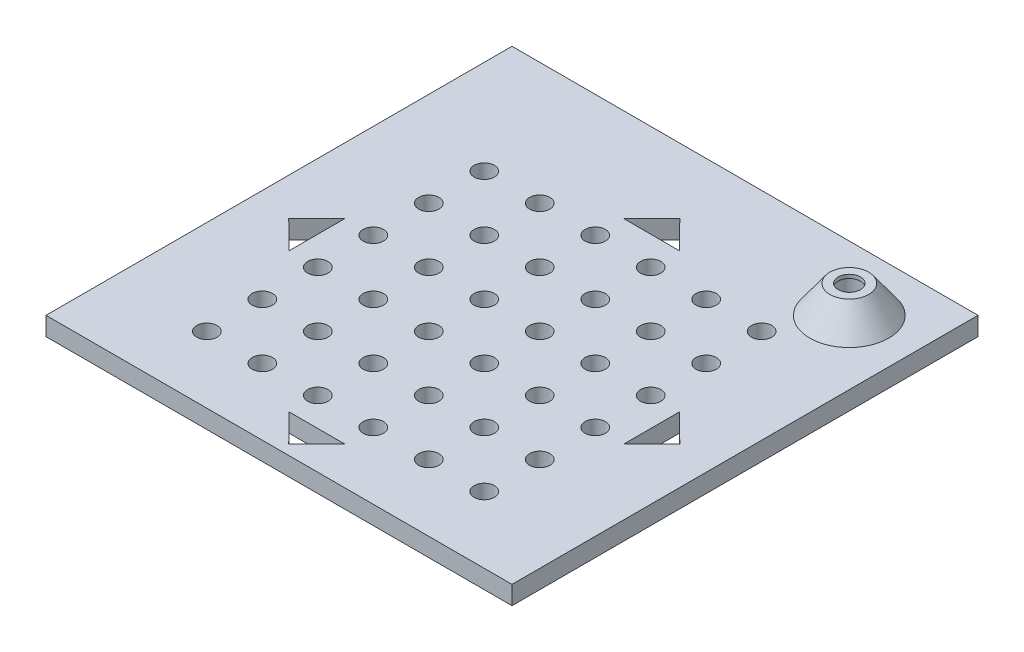
SolidWorks part; units mm, degrees
ref_plane "Front Plane" through (0, 0, 0) normal (0, 0, 1) x (1, 0, 0)
ref_plane "Top Plane" through (0, 0, 0) normal (0, 1, 0) x (1, 0, 0)
ref_plane "Right Plane" through (0, 0, 0) normal (1, 0, 0) x (0, 0, -1)
sketch "Sketch1" plane through (0, 0, 0) normal (0, 1, 0) x (1, 0, 0)
  line L1 (0, 0) -> (126, 0)
  line L2 (0, 0) -> (0, 126)
  line L3 (0, 126) -> (126, 126)
  line L4 (126, 0) -> (126, 126)
  dimension "D1" = 126
  dimension "D2" = 126
extrude "Boss-Extrude1" add sketch "Sketch1" along normal blind 5
sketch "Sketch3" plane through (0, 5, 0) normal (0, 1, 0) x (1, 0, 0)
  line L0 (108.6, 121.1) -> (108.6, 96.1) construction
  circle A0 centre (108.6, 108.6) radius 12.5
extrude "Boss-Extrude2" add sketch "Sketch3" along normal blind 7.5
sketch "Sketch4" plane through (0, 0, 0) normal (0, -1, 0) x (1, 0, 0)
  circle A1 centre (108.6, -108.6) radius 3.45
  dimension "D1" = 6.9
extrude "Cut-Extrude1" cut sketch "Sketch4" against normal blind 11.5
sketch "Sketch6" plane through (0, 12.5, 0) normal (0, 1, 0) x (1, 0, 0)
  line L0 (108.6, 121.1) -> (108.6, 96.1) construction
  circle A0 centre (108.6, 108.6) radius 12.5 construction
  circle A1 centre (108.6, 108.6) radius 3
  dimension "D1" = 6
extrude "Cut-Extrude2" cut sketch "Sketch6" against normal through all
chamfer "Chamfer1" distance 10 angle 36 1 edges at (108.6, 12.5, -96.1) first distance on face at (108.6, 12.5, -96.1)
sketch "Sketch7" plane through (0, 5, 0) normal (0, 1, 0) x (1, 0, 0)
  line L0 (94.5, 63) -> (94.5, 126) construction
  line L1 (126, 126) -> (0, 126) construction
  line L2 (0, 0) -> (126, 0) construction
  line L3 (31.5, 63) -> (31.5, 0) construction
  line L4 (55.5, 60.25) -> (55.5, 50.75) construction
  line L5 (63, 63) -> (58.25, 63) construction
  line L6 (63, 63) -> (67.75, 63) construction
  line L7 (31.5, 63) -> (31.5, 126) construction
  line L8 (52.75, 63) -> (43.25, 63) construction
  line L9 (55.5, 45.25) -> (55.5, 35.75) construction
  line L10 (63, 63) -> (63, 126) construction
  line L11 (63, 63) -> (63, 0) construction
  line L12 (94.5, 63) -> (94.5, 0) construction
  line L13 (73.25, 63) -> (82.75, 63) construction
  line L14 (88.25, 63) -> (97.75, 63) construction
  line L15 (37.75, 63) -> (28.25, 63) construction
  line L16 (55.5, 30.25) -> (55.5, 20.75) construction
  line L17 (55.5, 75.25) -> (55.5, 65.75) construction
  circle A0 centre (55.5, 63) radius 2.75
  circle A1 centre (70.5, 63) radius 2.75
  circle A2 centre (40.5, 63) radius 2.75
  circle A3 centre (85.5, 63) radius 2.75
  circle A4 centre (25.5, 63) radius 2.75
  circle A5 centre (100.5, 63) radius 2.75
  circle A6 centre (25.5, 48) radius 2.75
  circle A7 centre (40.5, 48) radius 2.75
  circle A8 centre (55.5, 48) radius 2.75
  circle A9 centre (70.5, 48) radius 2.75
  circle A10 centre (85.5, 48) radius 2.75
  circle A11 centre (100.5, 48) radius 2.75
  circle A12 centre (25.5, 33) radius 2.75
  circle A13 centre (40.5, 33) radius 2.75
  circle A14 centre (55.5, 33) radius 2.75
  circle A15 centre (70.5, 33) radius 2.75
  circle A16 centre (85.5, 33) radius 2.75
  circle A17 centre (100.5, 33) radius 2.75
  circle A18 centre (25.5, 18) radius 2.75
  circle A19 centre (40.5, 18) radius 2.75
  circle A20 centre (55.5, 18) radius 2.75
  circle A21 centre (70.5, 18) radius 2.75
  circle A22 centre (85.5, 18) radius 2.75
  circle A23 centre (100.5, 18) radius 2.75
  circle A24 centre (25.5, 78) radius 2.75
  circle A25 centre (40.5, 78) radius 2.75
  circle A26 centre (55.5, 78) radius 2.75
  circle A27 centre (70.5, 78) radius 2.75
  circle A28 centre (85.5, 78) radius 2.75
  circle A29 centre (100.5, 78) radius 2.75
  circle A30 centre (25.5, 93) radius 2.75
  circle A31 centre (40.5, 93) radius 2.75
  circle A32 centre (55.5, 93) radius 2.75
  circle A33 centre (70.5, 93) radius 2.75
  circle A34 centre (85.5, 93) radius 2.75
  circle A35 centre (100.5, 93) radius 2.75
  dimension "D1" = 5.5
  dimension "D2" = 4.75
  dimension "D3" = 4.75
  dimension "D4" = 9.5
  dimension "D5" = 9.5
  dimension "D6" = 9.5
  dimension "D7" = 9.5
  dimension "D9" = 9.5
  dimension "D10" = 3
  dimension "D11" = 9.5
  dimension "D8" = 4
extrude "Cut-Extrude3" cut sketch "Sketch7" against normal through all
sketch "Sketch8" plane through (0, 5, 0) normal (0, 1, 0) x (1, 0, 0)
  line L0 (22.75, 63) -> (17.75, 63) construction
  line L1 (103.25, 63) -> (108.25, 63) construction
  line L2 (55.5, 95.75) -> (55.5, 100.75) construction
  line L3 (70.5, 15.25) -> (70.5, 10.25) construction
  line L4 (70.5, 100.75) -> (63, 108.375)
  line L14 (108.25, 63) -> (115.875, 55.5)
  line L17 (55.5, 10.25) -> (63, 2.625)
  line L18 (63, 2.625) -> (63, 10.25) construction
  line L21 (70.5, 100.75) -> (55.5, 100.75)
  line L24 (17.75, 63) -> (17.75, 48)
  line L39 (55.5, 10.25) -> (70.5, 10.25)
  line L42 (17.75, 63) -> (10.125, 55.5)
  line L43 (70.5, 10.25) -> (63, 2.625)
  line L46 (55.5, 100.75) -> (63, 108.375)
  line L48 (17.75, 48) -> (10.125, 55.5)
  line L49 (108.25, 63) -> (108.25, 48)
  line L52 (108.25, 48) -> (115.875, 55.5)
  circle A0 centre (25.5, 63) radius 2.75 construction
  circle A1 centre (100.5, 63) radius 2.75 construction
  circle A2 centre (55.5, 93) radius 2.75 construction
  circle A3 centre (70.5, 18) radius 2.75 construction
  point P15 (63, 103.375)
  point P24 (114.625, 55.5)
  point P47 (63, 8.9645)
  dimension "D1" = 7.625
  dimension "D2" = 5
  dimension "D3" = 5
  dimension "D4" = 5
  dimension "D5" = 5
extrude "Cut-Extrude4" cut sketch "Sketch8" against normal through all
